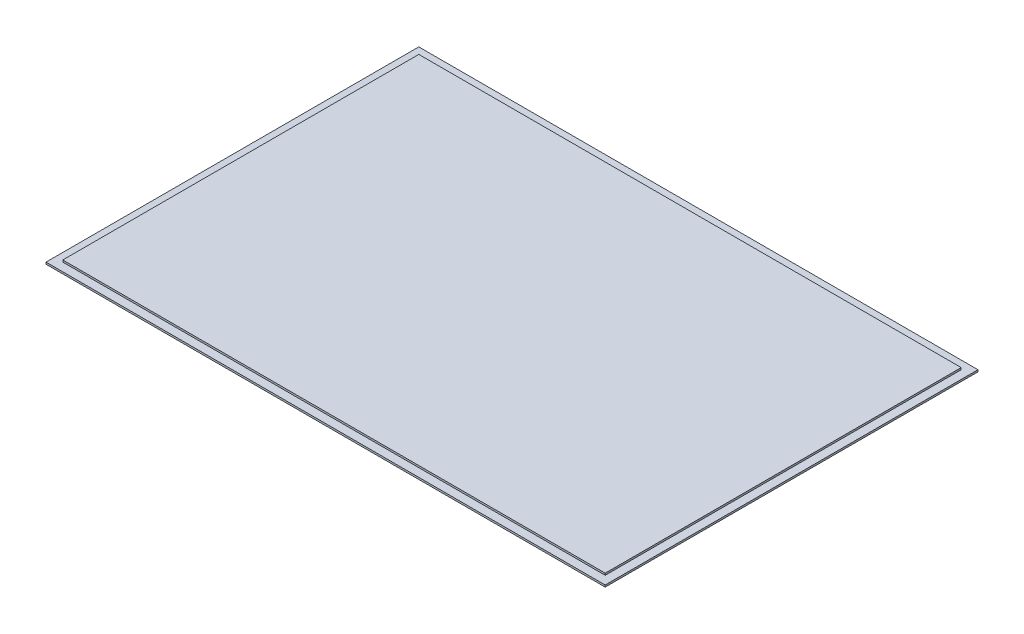
SolidWorks part; units mm, degrees
ref_plane "Front Plane" through (0, 0, 0) normal (0, 0, 1) x (1, 0, 0)
ref_plane "Top Plane" through (0, 0, 0) normal (0, 1, 0) x (1, 0, 0)
ref_plane "Right Plane" through (0, 0, 0) normal (1, 0, 0) x (0, 0, -1)
sketch "Sketch1" plane through (0, 0, 0) normal (0, 1, 0) x (1, 0, 0)
  line L0 (9, 9) -> (9, 391)
  line L1 (0, 0) -> (600, 0)
  line L2 (0, 0) -> (0, 400)
  line L3 (0, 400) -> (600, 400)
  line L4 (600, 0) -> (600, 400)
  line L5 (9, 391) -> (591, 391)
  line L6 (591, 9) -> (591, 391)
  line L7 (9, 9) -> (591, 9)
  dimension "D1" = 400
  dimension "D2" = 600
  dimension "D3" = 9
extrude "Boss-Extrude1" add sketch "Sketch1" along normal blind 2 contours L0 L7 L6 L5 | L1 L4 L3 L2 L7 L0 L5 L6 region at (300, 0, -200) region at (7.2111, 0, -200)
extrude "Boss-Extrude2" add sketch "Sketch1<3>" along normal blind 4 contours L0 L7 L6 L5 region at (300, 0, -200)
sketch "Sketch1<3>" plane through (0, 0, 0) normal (0, 1, 0) x (1, 0, 0) same geometry as "Sketch1"
